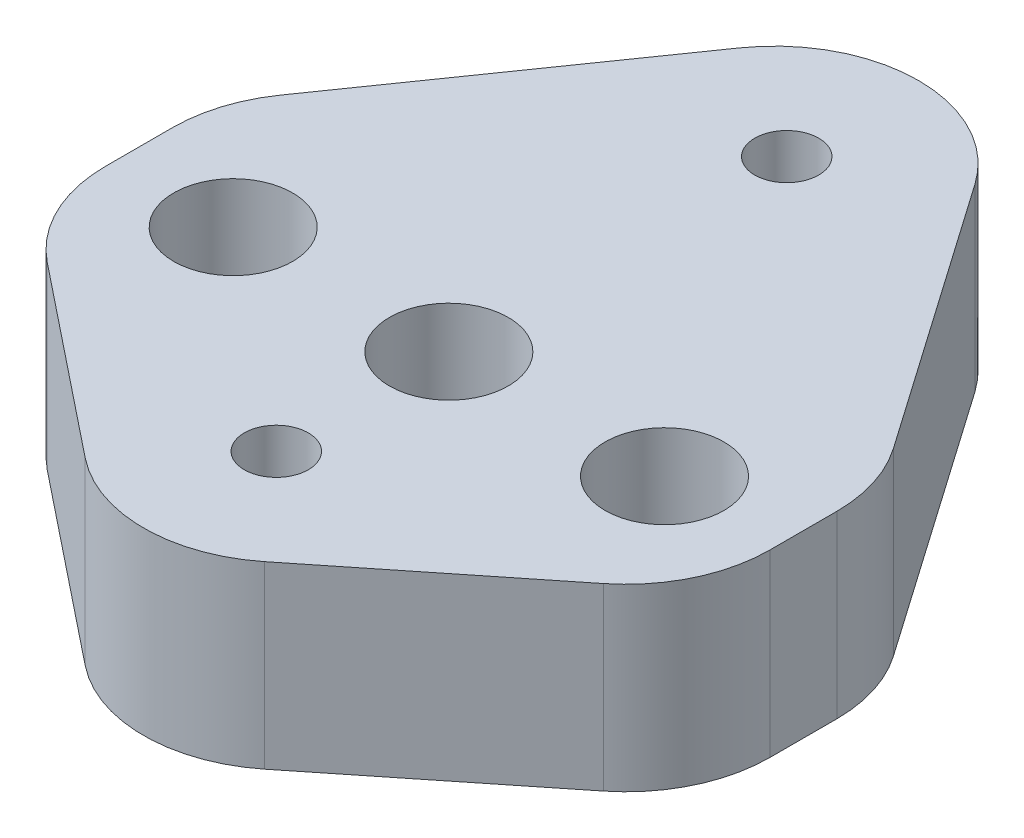
SolidWorks part; units mm, degrees
ref_plane "Front Plane" through (0, 0, 0) normal (0, 0, 1) x (1, 0, 0)
ref_plane "Top Plane" through (0, 0, 0) normal (0, 1, 0) x (1, 0, 0)
ref_plane "Right Plane" through (0, 0, 0) normal (1, 0, 0) x (0, 0, -1)
sketch "Sketch1" plane through (0, 0, 0) normal (0, 1, 0) x (1, 0, 0)
  line L0 (-4.1664, 14.4225) -> (-10.8242, 4.8788)
  line L1 (0, -1000) -> (0, 49000) construction
  line L2 (-9.8279, -4.3608) -> (-3.17, -9.6778)
  line L3 (4.1664, 14.4225) -> (10.8242, 4.8788)
  line L4 (-11.7379, -0.3913) -> (-11.7379, 1.9723)
  line L5 (11.7379, -0.3913) -> (11.7379, 1.9723)
  line L6 (9.8279, -4.3608) -> (3.17, -9.6778)
  circle A0 centre (-7.62, 0) radius 2.1
  circle A1 centre (0, 0) radius 2.1
  circle A2 centre (7.62, 0) radius 2.1
  circle A3 centre (0, 11.938) radius 1.1303
  circle A4 centre (0, -6.096) radius 1.1303
  arc A5 (-3.17, -9.6778) -> (3.17, -9.6778) centre (0, -5.7083) ccw
  arc A6 (-4.1664, 14.4225) -> (4.1664, 14.4225) centre (0, 11.516) cw
  arc A7 (10.8242, 4.8788) -> (11.7379, 1.9723) centre (6.6579, 1.9723) cw
  arc A8 (11.7379, -0.3913) -> (9.8279, -4.3608) centre (6.6579, -0.3913) cw
  arc A9 (-10.8242, 4.8788) -> (-11.7379, 1.9723) centre (-6.6579, 1.9723) ccw
  arc A10 (-9.8279, -4.3608) -> (-11.7379, -0.3913) centre (-6.6579, -0.3913) cw
  point P16 (0, -13.716)
  point P23 (0, 18.288)
  point P27 (11.7379, 3.5691)
  point P30 (11.7379, -2.8356)
  point P33 (-11.7379, 3.5691)
  point P36 (-11.7379, -2.8356)
  dimension "D3" = 7.62
  dimension "D4" = 2.2606
  dimension "D2" = 4.2
  dimension "D6" = 6.096
  dimension "D9" = 5.08
  dimension "D10" = 5.08
  dimension "D11" = 5.08
  dimension "D1" = 3
  dimension "D5" = 11.938
  dimension "D7" = 7.62
  dimension "D8" = 6.35
extrude "Boss-Extrude1" add sketch "Sketch1" along normal blind 6.35
